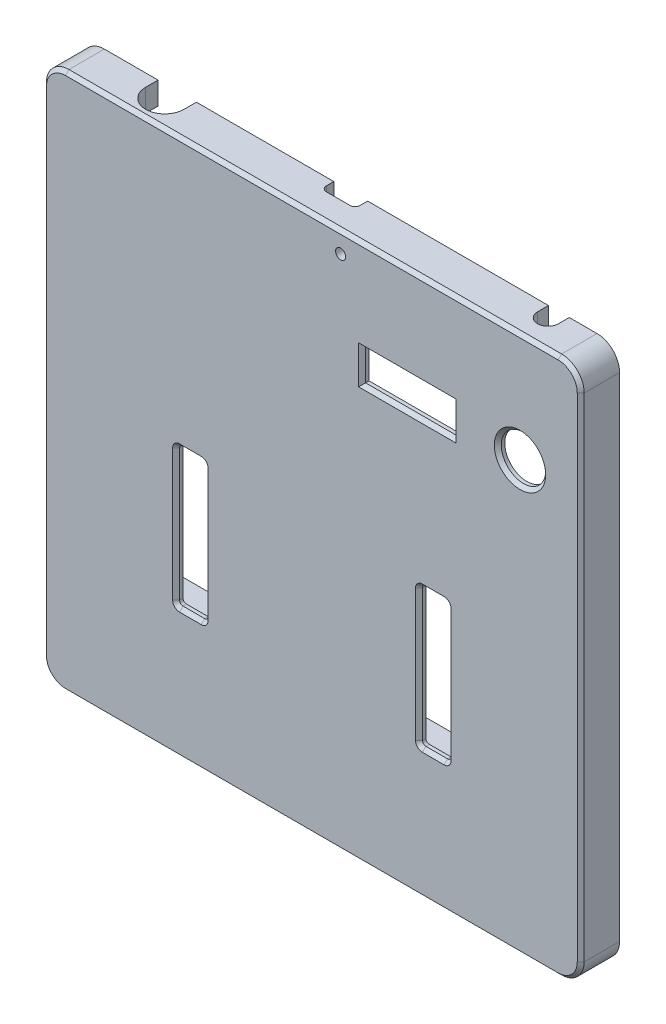
SolidWorks part; units mm, degrees
ref_plane "Front Plane" through (0, 0, 0) normal (0, 0, 1) x (1, 0, 0)
ref_plane "Top Plane" through (0, 0, 0) normal (0, 1, 0) x (1, 0, 0)
ref_plane "Right Plane" through (0, 0, 0) normal (1, 0, 0) x (0, 0, -1)
sketch "Sketch2" plane through (0, 0, 24.2113) normal (0, 0, 1) x (1, 0, 0)
  line L31 (-149.0776, 189.3324) -> (-32.2979, 189.3324) construction
  line L32 (-25.7979, 182.8324) -> (-25.7979, 40.8324) construction
  line L35 (-32.2979, 34.3324) -> (-174.2979, 34.3324) construction
  line L36 (-180.7979, 40.8324) -> (-180.7979, 182.8324) construction
  line L37 (-174.2979, 189.3324) -> (-32.2979, 189.3324)
  line L38 (-25.7979, 182.8324) -> (-25.7979, 40.8324)
  line L39 (-32.2979, 34.3324) -> (-174.2979, 34.3324)
  line L40 (-180.7979, 40.8324) -> (-180.7979, 182.8324)
  line L41 (-174.2979, 177.8324) -> (-174.2979, 119.8346)
  line L43 (-32.2979, 68.8301) -> (-32.2979, 114.8346)
  line L44 (-37.2979, 182.8324) -> (-93.5979, 182.8324)
  line L45 (-96.3979, 182.8324) -> (-96.3979, 180.8324)
  line L46 (-96.3979, 180.8324) -> (-93.5979, 180.8324)
  line L47 (-93.5979, 180.8324) -> (-93.5979, 182.8324)
  line L48 (-95.3979, 183.8824) -> (-95.3979, 182.9824) construction
  line L49 (-94.5979, 183.8824) -> (-94.5979, 182.9824) construction
  line L50 (-169.2979, 182.8324) -> (-174.2979, 177.8324)
  line L51 (-32.2979, 177.8324) -> (-37.2979, 182.8324)
  line L52 (-105.2282, 114.8346) -> (-105.2282, 68.8301)
  line L53 (-174.2979, 119.8346) -> (-32.2979, 119.8346)
  line L55 (-174.2979, 114.8346) -> (-105.2282, 114.8346)
  line L57 (-105.2282, 68.8301) -> (-174.2979, 68.8301)
  line L58 (-96.3979, 182.8324) -> (-169.2979, 182.8324)
  line L59 (-105.2282, 91.8324) -> (-103.2979, 91.8324) construction
  line L60 (-135.3134, 109.8346) -> (-139.7584, 109.8346) construction
  line L61 (-139.7584, 73.8301) -> (-135.3134, 73.8301) construction
  line L62 (-101.3676, 114.8346) -> (-101.3676, 68.8301)
  line L63 (-101.3676, 68.8301) -> (-32.2979, 68.8301)
  line L64 (-103.2979, 91.8324) -> (-101.3676, 91.8324) construction
  line L65 (-101.3676, 114.8346) -> (-32.2979, 114.8346)
  line L66 (-174.2979, 114.8346) -> (-174.2979, 68.8301)
  line L67 (-32.2979, 119.8346) -> (-32.2979, 177.8324)
  arc A1 (-25.7979, 182.8324) -> (-32.2979, 189.3324) centre (-32.2979, 182.8324) ccw construction
  arc A5 (-32.2979, 34.3324) -> (-25.7979, 40.8324) centre (-32.2979, 40.8324) ccw construction
  arc A6 (-180.7979, 40.8324) -> (-174.2979, 34.3324) centre (-174.2979, 40.8324) ccw construction
  arc A7 (-174.2979, 189.3324) -> (-180.7979, 182.8324) centre (-174.2979, 182.8324) ccw construction
  arc A8 (-25.7979, 182.8324) -> (-32.2979, 189.3324) centre (-32.2979, 182.8324) ccw
  arc A9 (-32.2979, 34.3324) -> (-25.7979, 40.8324) centre (-32.2979, 40.8324) ccw
  arc A10 (-180.7979, 40.8324) -> (-174.2979, 34.3324) centre (-174.2979, 40.8324) ccw
  arc A11 (-174.2979, 189.3324) -> (-180.7979, 182.8324) centre (-174.2979, 182.8324) ccw
  line M2 (-149.0776, 189.3324) -> (-149.0776, 187.3324)
  line M3 (-149.0776, 187.3324) -> (-32.2979, 187.3324)
  arc M4 (-32.2979, 187.3324) -> (-27.7979, 182.8324) centre (-32.2979, 182.8324) cw
  line M5 (-27.7979, 182.8324) -> (-27.7979, 40.8324)
  arc M6 (-27.7979, 40.8324) -> (-32.2979, 36.3324) centre (-32.2979, 40.8324) cw
  line M7 (-32.2979, 36.3324) -> (-174.2979, 36.3324)
  arc M8 (-174.2979, 36.3324) -> (-178.7979, 40.8324) centre (-174.2979, 40.8324) cw
  line M9 (-178.7979, 40.8324) -> (-178.7979, 182.8324)
  arc M10 (-178.7979, 182.8324) -> (-174.2979, 187.3324) centre (-174.2979, 182.8324) cw
  line M11 (-174.2979, 187.3324) -> (-157.5182, 187.3324)
  line M12 (-157.5182, 187.3324) -> (-157.5182, 189.3324)
  line M13 (-157.5182, 189.3324) -> (-174.2979, 189.3324)
  arc M14 (-174.2979, 189.3324) -> (-180.7979, 182.8324) centre (-174.2979, 182.8324) ccw
  line M15 (-180.7979, 182.8324) -> (-180.7979, 40.8324)
  arc M16 (-180.7979, 40.8324) -> (-174.2979, 34.3324) centre (-174.2979, 40.8324) ccw
  line M17 (-174.2979, 34.3324) -> (-32.2979, 34.3324)
  arc M18 (-32.2979, 34.3324) -> (-25.7979, 40.8324) centre (-32.2979, 40.8324) ccw
  line M19 (-25.7979, 40.8324) -> (-25.7979, 182.8324)
  arc M20 (-25.7979, 182.8324) -> (-32.2979, 189.3324) centre (-32.2979, 182.8324) ccw
  line M21 (-32.2979, 189.3324) -> (-149.0776, 189.3324)
  dimension "D1" = 1
  dimension "D2" = 1
  dimension "D3" = 2
  dimension "D4" = 5
  dimension "D5" = 5
  dimension "D6" = 5
extrude "Boss-Extrude1" add sketch "Sketch2" along normal offset from surface (9.2009 mm away) 1 contours L37 L67 L53 L41 L50 L44 L51 L66 L55 L52 L57 L62 L65 L43 L63 M12 M11 M10 M9 M8 M7 M6 M5 M4 M3 M2 | M21 M2 M3 M4 M5 M6 M7 M8 M9 M10 M11 M12 M13 M14 M15 M16 M17 M18 M19 M20 region at (-165.908, 189.1132, 24.2113) region at (-103.4038, 82.2393, 24.2113)
fillet "Fillet1" radius 4 14 edges at (-32.2979, 114.8346, 28.8117) (-32.2979, 68.8301, 28.8117) (-101.3676, 68.8301, 28.8117) (-174.2979, 68.8301, 28.8117) (-105.2282, 68.8301, 28.8117) (-174.2979, 114.8346, 28.8117) (-105.2282, 114.8346, 28.8117) (-101.3676, 114.8346, 28.8117) (-37.2979, 182.8324, 28.8117) (-32.2979, 177.8324, 28.8117) (-32.2979, 119.8346, 28.8117) (-174.2979, 119.8346, 28.8117) (-174.2979, 177.8324, 28.8117) (-169.2979, 182.8324, 28.8117)
sketch "Sketch4" plane through (0, 0, 33.4122) normal (0, 0, 1) x (1, 0, 0)
  line L8 (-174.2979, 34.3324) -> (-32.2979, 34.3324) construction
  line L9 (-25.7979, 40.8324) -> (-25.7979, 182.8324) construction
  line L10 (-174.2979, 189.3324) -> (-32.2979, 189.3324) construction
  line L11 (-180.7979, 182.8324) -> (-180.7979, 40.8324) construction
  line L12 (-174.2979, 34.3324) -> (-32.2979, 34.3324)
  line L13 (-25.7979, 40.8324) -> (-25.7979, 182.8324)
  line L14 (-174.2979, 189.3324) -> (-32.2979, 189.3324)
  line L15 (-180.7979, 182.8324) -> (-180.7979, 40.8324)
  arc A8 (-180.7979, 40.8324) -> (-174.2979, 34.3324) centre (-174.2979, 40.8324) ccw construction
  arc A9 (-32.2979, 34.3324) -> (-25.7979, 40.8324) centre (-32.2979, 40.8324) ccw construction
  arc A10 (-25.7979, 182.8324) -> (-32.2979, 189.3324) centre (-32.2979, 182.8324) ccw construction
  arc A11 (-174.2979, 189.3324) -> (-180.7979, 182.8324) centre (-174.2979, 182.8324) ccw construction
  arc A12 (-180.7979, 40.8324) -> (-174.2979, 34.3324) centre (-174.2979, 40.8324) ccw
  arc A13 (-32.2979, 34.3324) -> (-25.7979, 40.8324) centre (-32.2979, 40.8324) ccw
  arc A14 (-25.7979, 182.8324) -> (-32.2979, 189.3324) centre (-32.2979, 182.8324) ccw
  arc A15 (-174.2979, 189.3324) -> (-180.7979, 182.8324) centre (-174.2979, 182.8324) ccw
extrude "Boss-Extrude2" add sketch "Sketch4" along normal blind 2
sketch "Sketch5" plane through (0, 0, 35.4122) normal (0, 0, 1) x (1, 0, 0)
  circle A0 centre (-43.2979, 157.8824) radius 6.4
  arc A3 (-49.1875, 157.5324) -> (-49.1875, 158.2324) centre (-43.2979, 157.8824) ccw construction
  dimension "D1" = 0.5
extrude "Cut-Extrude2" cut sketch "Sketch5" against normal up to next
sketch "Sketch9" plane through (0, 189.3324, 0) normal (0, 1, 0) x (1, 0, 0)
  line L0 (-174.2979, -24.2113) -> (-32.2979, -24.2113) construction
  line L2 (-158.8229, -27.7771) -> (-158.8229, -24.2113)
  line L3 (-158.8229, -24.2113) -> (-147.7729, -24.2113)
  line L4 (-147.7729, -27.7771) -> (-147.7729, -24.2113)
  line L5 (-149.0776, -24.2113) -> (-32.2979, -24.2113) construction
  line L7 (-46.2979, -27.3455) -> (-46.2979, -24.2113)
  line L8 (-46.2979, -24.2113) -> (-40.2979, -24.2113)
  line L9 (-40.2979, -27.3455) -> (-40.2979, -24.2113)
  line L12 (-98.4229, -24.1455) -> (-108.1729, -24.1455)
  line L13 (-108.1729, -24.1455) -> (-108.1729, -26.3455)
  line L14 (-106.6729, -27.8455) -> (-99.9229, -27.8455)
  line L16 (-98.4229, -24.1455) -> (-98.4229, -26.3455)
  arc A1 (-108.1729, -26.3455) -> (-106.6729, -27.8455) centre (-106.6729, -26.3455) ccw
  arc A2 (-158.8229, -27.7771) -> (-147.7729, -27.7771) centre (-153.2979, -27.7771) ccw
  arc A3 (-46.2979, -27.3455) -> (-40.2979, -27.3455) centre (-43.2979, -27.3455) ccw
  circle A4 centre (-43.2979, -27.3455) radius 2.5 construction
  arc A5 (-98.4229, -26.3455) -> (-99.9229, -27.8455) centre (-99.9229, -26.3455) cw
  point P29 (-108.1729, -27.8455)
  dimension "D1" = 0.5
  dimension "D4" = 1.5
  dimension "D2" = 3.7
extrude "Cut-Extrude6" cut sketch "Sketch9" against normal up to next
sketch "Sketch7" plane through (0, 0, 35.4122) normal (0, 0, 1) x (1, 0, 0)
  line L25 (-137.0203, 111.8324) -> (-137.0203, 109.8346) construction
  line L26 (-134.1729, 71.8324) -> (-142.4229, 71.8324)
  line L27 (-134.1729, 71.8324) -> (-134.1729, 111.8324)
  line L28 (-134.1729, 111.8324) -> (-142.4229, 111.8324)
  line L29 (-142.4229, 71.8324) -> (-142.4229, 111.8324)
  line L30 (-135.3134, 109.8346) -> (-139.7584, 109.8346) construction
  line L31 (-142.4229, 107.7094) -> (-141.2824, 107.7094) construction
  line L32 (-141.2824, 108.3106) -> (-141.2824, 75.3541) construction
  line L33 (-134.1729, 108.4616) -> (-135.3134, 108.4616) construction
  line L34 (-135.3134, 73.8301) -> (-135.3134, 109.8346) construction
  line L35 (-136.173, 71.8324) -> (-136.173, 73.8301) construction
  line L36 (-139.7584, 73.8301) -> (-135.3134, 73.8301) construction
  dimension "D3" = 8.25
  dimension "D4" = 40
extrude "Cut-Extrude4" cut sketch "Sketch7" against normal up to next
fillet "Fillet4" radius 1 4 edges at (-142.4229, 71.8324, 34.4122) (-134.1729, 71.8324, 34.4122) (-134.1729, 111.8324, 34.4122) (-142.4229, 111.8324, 34.4122)
pattern_linear "LPattern1" count 2 spacing 70 along (1, 0, 0) of "Fillet4", "Cut-Extrude4"
sketch "Sketch8" plane through (0, 0, 35.4122) normal (0, 0, 1) x (1, 0, 0)
  line L1 (-62.7979, 153.864) -> (-88.7979, 153.864)
  line L2 (-62.7979, 153.864) -> (-62.7979, 162.864)
  line L3 (-62.7979, 162.864) -> (-88.7979, 162.864)
  line L4 (-88.7979, 153.864) -> (-88.7979, 162.864)
  line L6 (-25.7979, 40.8324) -> (-25.7979, 182.8324) construction
  dimension "D1" = 26
  dimension "D2" = 9
  dimension "D4" = 37
extrude "Cut-Extrude5" cut sketch "Sketch8" against normal up to next
chamfer "Chamfer1" distance 1 angle 45 29 edges at (-36.8979, 157.8824, 35.4122) (-75.7979, 162.864, 35.4122) (-88.7979, 158.364, 35.4122) (-75.7979, 153.864, 35.4122) (-62.7979, 158.364, 35.4122) (-180.7979, 111.8324, 35.4122) (-178.8941, 187.4286, 35.4122) (-103.2979, 189.3324, 35.4122) (-27.7017, 187.4286, 35.4122) (-25.7979, 111.8324, 35.4122) (-27.7017, 36.2362, 35.4122) (-103.2979, 34.3324, 35.4122) (-178.8941, 36.2362, 35.4122) (-134.4658, 111.5395, 35.4122) (-138.2979, 111.8324, 35.4122) (-142.13, 111.5395, 35.4122) (-142.4229, 91.8324, 35.4122) (-142.13, 72.1253, 35.4122) (-138.2979, 71.8324, 35.4122) (-134.4658, 72.1253, 35.4122) (-134.1729, 91.8324, 35.4122) (-64.4658, 111.5395, 35.4122) (-68.2979, 111.8324, 35.4122) (-72.13, 111.5395, 35.4122) (-72.4229, 91.8324, 35.4122) (-72.13, 72.1253, 35.4122) (-68.2979, 71.8324, 35.4122) (-64.4658, 72.1253, 35.4122) (-64.1729, 91.8324, 35.4122)
fillet "Fillet5" radius 2 2 edges at (-96.3979, 182.8324, 28.8117) (-93.5979, 182.8324, 28.8117)
fillet "Fillet6" radius 2 2 edges at (-93.5979, 180.8324, 28.8117) (-96.3979, 180.8324, 28.8117)
sketch "Sketch10" plane through (0, 0, 35.4122) normal (0, 0, 1) x (1, 0, 0)
  circle A0 centre (-94.9979, 183.4324) radius 1.4605
  point P2 (-94.9979, 183.4324)
  dimension "D1" = 2.921
extrude "Cut-Extrude11" cut sketch "Sketch10" along direction (0, 0, -1) on the side against the normal through all
sketch "Sketch11" plane through (0, 0, 24.2113) normal (0, 0, -1) x (-1, 0, 0)
  point P0 (32.2979, 182.8324)
  point P1 (174.2979, 40.8324)
  point P3 (32.2979, 40.8324)
  point P4 (174.2979, 182.8324)
  point P5 (0, 0)
  point P6 (174.2979, 182.8324)
  point P8 (0, 0)
  point P9 (174.2979, 40.8324)
  point P11 (0, 0)
  point P12 (32.2979, 40.8324)
hole_wizard "M3x0.5 Tapped Hole1" positions "3DSketch2" profile "Sketch12" tap size "M3x0.5" standard "ANSI Metric"
sketch3d "3DSketch2"
  line L0 (-174.2979, 40.8324, 24.0955) -> (-174.2979, 40.8324, 22.5113) construction
  line L1 (-174.2979, 182.8324, 24.0955) -> (-174.2979, 182.8324, 22.5113) construction
  line L2 (-32.2979, 182.8324, 24.0955) -> (-32.2979, 182.8324, 22.5113) construction
  line L3 (-32.2979, 40.8324, 24.0955) -> (-32.2979, 40.8324, 22.5113) construction
  point P0 (-174.2979, 40.8324, 22.5113)
  point P4 (-174.2979, 182.8324, 22.5113)
  point P8 (-32.2979, 182.8324, 22.5113)
  point P12 (-32.2979, 40.8324, 22.5113)
sketch "Sketch12" plane through (-174.2979, 40.8324, 22.5113) normal (1, 0, 0) x (0, 1, 0)
  line L0 (0, 0) -> (0, 10.7511)
  line L1 (0, 10.7511) -> (1.25, 10)
  line L2 (1.25, 10) -> (1.25, 0)
  line L5 (1.25, 0) -> (0, 0)
  line L10 (0, 10.7511) -> (-1.25, 10) construction
  line L11 (0, -6.35) -> (0, 107.95) construction
  dimension "Tap Drill Dia." = 2.5
  dimension "Tap Drill Depth" = 10
  dimension "Drill Angle" = 118
cosmetic thread "Hole Thread1" parameters "D1"=7, "D2"=3
cosmetic thread "Hole Thread2" parameters "D1"=7, "D2"=3
cosmetic thread "Hole Thread3" parameters "D1"=7, "D2"=3
cosmetic thread "Hole Thread4" parameters "D1"=7, "D2"=3
